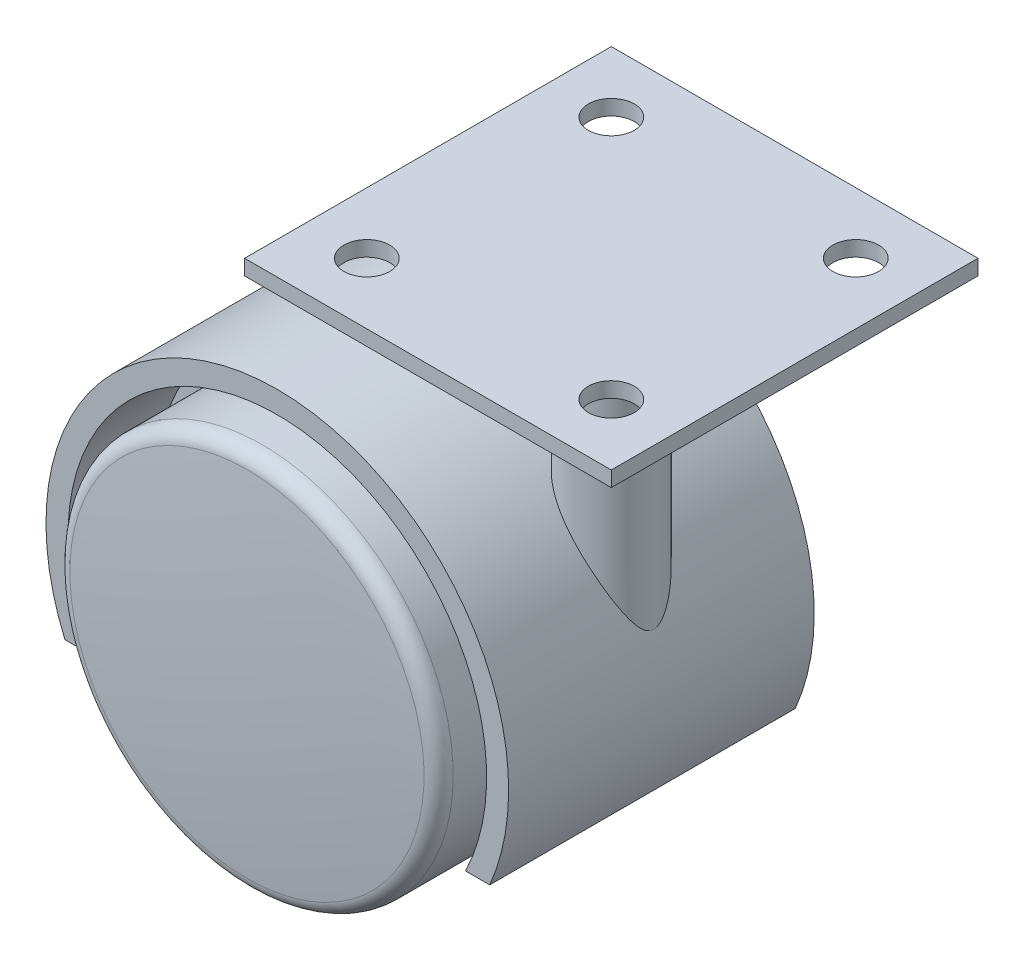
SolidWorks part; units mm, degrees
ref_plane "Front Plane" through (0, 0, 0) normal (0, 0, 1) x (1, 0, 0)
ref_plane "Top Plane" through (0, 0, 0) normal (0, 1, 0) x (1, 0, 0)
ref_plane "Right Plane" through (0, 0, 0) normal (1, 0, 0) x (0, 0, -1)
sketch "Sketch1" plane through (0, 0, 0) normal (0, 0, 1) x (1, 0, 0)
  line L0 (0, -19.8438) -> (18.8277, -19.8438) construction
  line L1 (18.8277, -19.8438) -> (18.8277, 37.3062) construction
  line L2 (23.241, 37.3062) -> (14.4145, 37.3062) construction
  line L4 (14.4145, 37.3062) -> (14.4145, 19.2326) construction
  line L5 (23.241, 37.3062) -> (23.241, -6.1258) construction
  line L6 (-22.0668, -9.525) -> (22.0668, -9.525) construction
  line L7 (0, 19.8438) -> (0, 21.7488) construction
  line L8 (-0.2223, 37.3062) -> (37.8777, 37.3062)
  line L9 (-0.2223, 37.3062) -> (-0.2223, 35.7188)
  line L10 (-0.2223, 35.7188) -> (37.8777, 35.7188)
  line L11 (37.8777, 37.3062) -> (37.8777, 35.7188)
  circle A0 centre (0, 0) radius 19.8438
  arc A1 (19.552, -9.525) -> (-19.552, -9.525) centre (0, 0) ccw construction
  arc A2 (22.0668, -9.525) -> (-22.0668, -9.525) centre (0, 0) ccw construction
  circle A4 centre (0, 0) radius 24.0348 construction
  circle A5 centre (0, 0) radius 21.7488 construction
  point P10 (18.8277, 37.3062)
  point P14 (27.305, 0)
  point P16 (29.591, 0)
  dimension "Wheel Dia" = 39.6875
  dimension "D1" = 1.905
  dimension "D2" = 42.8625
  dimension "Mount Height" = 57.15
  dimension "D9" = 9.525
  dimension "Plate Thickness" = 1.5875
  dimension "Plate Length" = 38.1
  dimension "D7" = 2.286
sketch "Sketch16" plane through (0, 0, 0) normal (0, 0, 1) x (1, 0, 0)
  line L1 (-0.2223, 37.3062) -> (37.8777, 37.3062)
  line L2 (-0.2223, 37.3062) -> (-0.2223, 35.7188)
  line L3 (-0.2223, 35.7188) -> (37.8777, 35.7188)
  line L4 (37.8777, 37.3062) -> (37.8777, 35.7188)
extrude "Boss-Extrude1" add sketch "Sketch16" along normal mid plane 38.1
sketch "Sketch17" plane through (0, 37.3062, 0) normal (0, 1, 0) x (1, 0, 0)
  line L0 (-0.2223, 19.05) -> (37.8777, -19.05) construction
  line L1 (18.8277, 0) -> (18.8277, 19.05) construction
  line L2 (18.8277, 0) -> (37.8777, 0) construction
  line L3 (-0.2223, 0) -> (37.8777, 0) construction
  line L4 (37.8777, -19.05) -> (37.8777, 19.05) construction
  line L5 (37.8777, 19.05) -> (-0.2223, 19.05) construction
  circle A0 centre (-1.016, 10.3187) radius 2.3812
  circle A1 centre (38.6715, 10.3187) radius 2.3812
  circle A2 centre (38.6715, -10.3187) radius 2.3812
  circle A3 centre (-1.016, -10.3187) radius 2.3812
  dimension "D1" = 4.7625
  dimension "D2" = 39.6875
  dimension "D3" = 20.6375
extrude "Plate 1 holes" [suppressed] cut sketch "Sketch17" against normal through all
sketch "Sketch18" plane through (0, 37.3062, 0) normal (0, 1, 0) x (1, 0, 0)
  line L0 (-0.2223, 19.05) -> (37.8777, -19.05) construction
  line L1 (18.8277, 0) -> (18.8277, 19.05) construction
  line L2 (18.8277, 0) -> (37.8777, 0) construction
  line L3 (37.8777, -19.05) -> (37.8777, 19.05) construction
  line L4 (37.8777, 19.05) -> (-0.2223, 19.05) construction
  circle A0 centre (6.1277, 12.7) radius 2.3813
  circle A1 centre (31.5277, 12.7) radius 2.3812
  circle A2 centre (31.5277, -12.7) radius 2.3812
  circle A3 centre (6.1277, -12.7) radius 2.3813
  dimension "D3" = 4.7625
  dimension "D1" = 25.4
  dimension "D2" = 25.4
extrude "Plate 2 holes" cut sketch "Sketch18" against normal through all
sketch "Sketch2" plane through (0, 0, 0) normal (1, 0, 0) x (0, 0, -1)
  line L0 (-19.8438, 0) -> (19.8438, 0) construction
  line L1 (-9.271, 4.7625) -> (-9.271, 19.8438)
  line L2 (-9.271, 19.8438) -> (-17.4441, 19.8438)
  line L3 (-19.8438, 0) -> (-19.8438, 19.8438) construction
  line L4 (-19.8438, 0) -> (0, 0)
  line L5 (0, 0) -> (0, 20.8454) construction
  line L6 (0, 21.7488) -> (0, -9.525) construction
  line L7 (19.8438, 0) -> (0, 0)
  line L8 (9.271, 19.8438) -> (17.4441, 19.8438)
  line L9 (9.271, 4.7625) -> (9.271, 19.8438)
  line L10 (-9.271, 4.7625) -> (9.271, 4.7625)
  line L11 (0, 0) -> (0, 4.7625) construction
  arc A0 (-19.0253, 18.3972) -> (-19.8438, 0) centre (187.3382, 0) ccw
  arc A1 (19.0253, 18.3972) -> (19.8438, 0) centre (-187.3382, 0) cw
  arc A2 (-17.4441, 19.8438) -> (-19.0253, 18.3972) centre (-17.4441, 18.2563) ccw
  arc A3 (19.0253, 18.3972) -> (17.4441, 19.8438) centre (17.4441, 18.2563) ccw
  point P19 (-18.8912, 19.8438)
  point P22 (18.8912, 19.8438)
  dimension "D6" = 1.5875
  dimension "Width" = 39.6875
  dimension "D2" = 39.6875
  dimension "D3" = 9.271
  dimension "D4" = 4.7625
  dimension "D5" = 0.9525
revolve "Revolve1" add sketch "Sketch2" angle 360 about L0
sketch "Sketch5" plane through (0, 0, 0) normal (0, 0, 1) x (1, 0, 0)
  line L0 (-22.0668, -9.525) -> (22.0668, -9.525) construction
  line L1 (-22.0668, -9.525) -> (-19.552, -9.525)
  line L2 (19.552, -9.525) -> (22.0668, -9.525)
  arc A0 (22.0668, -9.525) -> (-22.0668, -9.525) centre (0, 0) ccw construction
  arc A1 (19.552, -9.525) -> (-19.552, -9.525) centre (0, 0) ccw construction
  arc A2 (22.0668, -9.525) -> (-22.0668, -9.525) centre (0, 0) ccw
  arc A3 (19.552, -9.525) -> (-19.552, -9.525) centre (0, 0) ccw
extrude "Extrude1" add sketch "Sketch5" along normal mid plane 31.75 separate body
sketch "Sketch7" plane through (0, 0, 0) normal (0, 0, 1) x (1, 0, 0)
  line L0 (18.8277, 35.7188) -> (18.8278, 0)
  line L1 (18.8277, -19.8438) -> (18.8277, 37.3062) construction
  line L2 (-0.2223, 35.7188) -> (37.8777, 35.7188) construction
  line L3 (22.8917, 24.0347) -> (22.8917, 28.8353)
  line L4 (22.8917, 24.0347) -> (23.241, 24.0347)
  line L5 (23.241, 37.3062) -> (23.241, -6.1258) construction
  line L6 (23.241, 24.0347) -> (23.241, 0)
  line L7 (23.241, 0) -> (18.8278, 0)
  line L10 (22.8917, 28.8353) -> (23.9331, 28.8353)
  line L11 (23.9331, 32.7978) -> (30.5117, 35.7188)
  line L12 (18.8277, 35.7188) -> (30.5117, 35.7188)
  line L13 (18.8277, 35.7188) -> (18.8277, 37.3062) construction
  arc A0 (23.9331, 28.8353) -> (23.9331, 32.7978) centre (19.4711, 30.8165) ccw
  arc A1 (22.0668, -9.525) -> (-22.0668, -9.525) centre (0, 0) ccw construction
  dimension "D1" = 8.128
  dimension "D2" = 2.921
  dimension "D3" = 3.9624
  dimension "D5" = 1.0414
  dimension "D6" = 23.368
revolve "Revolve3" add sketch "Sketch7" angle 360 about L1
sketch "Sketch15" plane through (0, 0, 15.875) normal (0, 0, 1) x (1, 0, 0)
  arc A0 (19.552, -9.525) -> (-19.552, -9.525) centre (0, 0) ccw construction
  arc A1 (19.552, -9.525) -> (-19.552, -9.525) centre (0, 0) ccw
extrude "Extrude7" cut sketch "Sketch15" against normal through all and the other way through all
sketch "Sketch8" plane through (0, 0, 0) normal (0, 0, 1) x (1, 0, 0)
  line L0 (-22.0668, -9.525) -> (22.0668, -9.525) construction
  line L1 (-19.552, -9.525) -> (19.552, -9.525)
  arc A0 (19.552, -9.525) -> (-19.552, -9.525) centre (0, 0) ccw construction
  arc A1 (19.552, -9.525) -> (-19.552, -9.525) centre (0, 0) ccw
extrude "Extrude2" add sketch "Sketch8" along normal offset from surface 2.54 and the other way offset from surface 2.54 up to face at (0, -19.8438, 9.271) other way up to face at (0, -4.7625, -9.271)
combine bodies "Combine1" operation type add bodies to combine 107 105 102
sketch "Sketch11" [suppressed] plane through (0, 0, 0) normal (0, 0, 1) x (1, 0, 0)
  line L0 (-27.7643, 7.1501) -> (-49.2222, 7.1501)
  line L1 (-49.2222, 7.1501) -> (-49.2222, 11.9126)
  line L2 (-49.2222, 11.9126) -> (-31.485, 16.6653)
  line L3 (-33.5727, 11.9126) -> (-26.0782, 11.9126)
  circle A2 centre (0, 0) radius 28.6702 construction
  arc A3 (34.2268, -9.8771) -> (-34.2268, -9.8771) centre (0, 0) ccw
  arc A4 (-31.485, 16.6653) -> (-33.5727, 11.9126) centre (0, 0) ccw
  arc A5 (-26.0782, 11.9126) -> (-27.7643, 7.1501) centre (0, 0) ccw
  arc A6 (33.0066, -9.525) -> (-33.0066, -9.525) centre (0, 0) ccw construction
  point P3 (-33.6012, 7.1501)
  dimension "D5" = 15
  dimension "D1" = 1.27
  dimension "D2" = 7.1501
  dimension "D3" = 4.7625
  dimension "D4" = 15.621
extrude "Extrude3" [suppressed] add sketch "Sketch11" along normal mid plane 28.575 separate body
sketch "Sketch12" [suppressed] plane through (0, 0, 14.2875) normal (0, 0, 1) x (1, 0, 0)
  line L8 (-26.0782, 11.9126) -> (-33.5727, 11.9126)
  line L9 (-31.485, 16.6653) -> (-49.2222, 11.9126)
  line L10 (-49.2222, 11.9126) -> (-49.2222, 7.1501)
  line L11 (-49.2222, 7.1501) -> (-27.7643, 7.1501)
  line L12 (-26.0782, 11.9126) -> (-33.5727, 11.9126)
  line L15 (-34.8986, 7.1501) -> (-27.7643, 7.1501)
  arc A4 (-26.0782, 11.9126) -> (-27.7643, 7.1501) centre (0, 0) ccw
  arc A13 (-31.485, 16.6653) -> (-33.5727, 11.9126) centre (0, 0) ccw
  arc A14 (-26.0782, 11.9126) -> (-27.7643, 7.1501) centre (0, 0) ccw
  arc A15 (-33.5727, 11.9126) -> (-34.8986, 7.1501) centre (0, 0) ccw
  dimension "D1" = 0
extrude "Extrude4" [suppressed] cut sketch "Sketch12" against normal offset from surface (10.3251 mm away) 3.9624 up to plane "Front Plane"
sketch "Sketch13" [suppressed] plane through (0, 0, -14.2875) normal (0, 0, -1) x (-1, 0, 0)
  line L2 (27.7643, 7.1501) -> (34.8986, 7.1501)
  line L3 (27.7643, 7.1501) -> (34.8986, 7.1501)
  line L4 (33.5727, 11.9126) -> (26.0782, 11.9126)
  line L5 (33.5727, 11.9126) -> (26.0782, 11.9126)
  arc A2 (27.7643, 7.1501) -> (26.0782, 11.9126) centre (0, 0) ccw
  arc A3 (27.7643, 7.1501) -> (26.0782, 11.9126) centre (0, 0) ccw
  arc A4 (34.8986, 7.1501) -> (33.5727, 11.9126) centre (0, 0) ccw
  arc A5 (34.8986, 7.1501) -> (33.5727, 11.9126) centre (0, 0) ccw
  dimension "D1" = 0
extrude "Extrude5" [suppressed] cut sketch "Sketch13" against normal offset from surface (10.4775 mm away) 3.81 up to plane "Front Plane"
sketch "Sketch14" [suppressed] plane through (0, 0, 0) normal (0, 0, 1) x (1, 0, 0)
  line L0 (-31.5803, 5.5685) -> (-33.8316, 5.9654)
  line L1 (-20.6126, 24.5651) -> (-22.082, 26.3163)
  line L2 (0, 0) -> (-42.5121, 0) construction
  arc A0 (30.6202, -9.525) -> (-30.6202, -9.525) centre (0, 0) ccw construction
  arc A1 (33.0066, -9.525) -> (-33.0066, -9.525) centre (0, 0) ccw construction
  arc A2 (-20.6126, 24.5651) -> (-31.5803, 5.5685) centre (0, 0) ccw
  arc A3 (-22.082, 26.3163) -> (-33.8316, 5.9654) centre (0, 0) ccw
  dimension "D1" = 10
  dimension "D2" = 50
extrude "Extrude8" [suppressed] cut sketch "Sketch14" against normal mid plane 7.9375
equation "\"D5@Sketch2\" = \"D4@Sketch2\"/5"
equation "\"D1@Extrude1\" = \"Width@Sketch2\"*.80"
equation "\"D2@Sketch2\" = \"Wheel Dia@Sketch1\""
